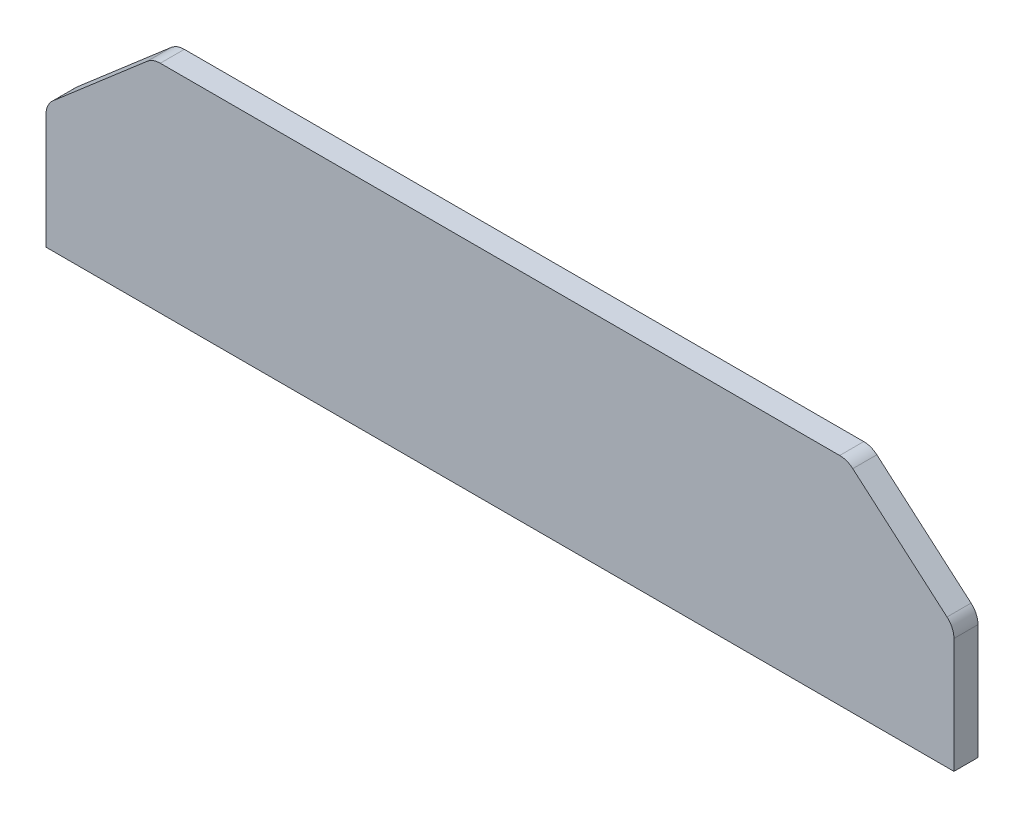
SolidWorks part; units mm, degrees
ref_plane "Front Plane" through (0, 0, 0) normal (0, 0, 1) x (1, 0, 0)
ref_plane "Top Plane" through (0, 0, 0) normal (0, 1, 0) x (1, 0, 0)
ref_plane "Right Plane" through (0, 0, 0) normal (1, 0, 0) x (0, 0, -1)
sketch "Sketch2" plane through (0, 3, 0) normal (0, 0, 1) x (1, 0, 0)
  line L2 (-56.625, -30) -> (56.625, -30)
  line L3 (56.625, -30) -> (56.625, -15.6446)
  line L4 (55.7585, -13.7521) -> (44.0052, -3.6075)
  line L5 (42.3717, -3) -> (-42.3717, -3)
  line L6 (-44.0052, -3.6075) -> (-55.7585, -13.7521)
  line L7 (-56.625, -15.6446) -> (-56.625, -30)
  arc A0 (56.625, -15.6446) -> (55.7585, -13.7521) centre (54.125, -15.6446) ccw
  arc A1 (44.0052, -3.6075) -> (42.3717, -3) centre (42.3717, -5.5) ccw
  arc A2 (-55.7585, -13.7521) -> (-56.625, -15.6446) centre (-54.125, -15.6446) ccw
  arc A3 (-42.3717, -3) -> (-44.0052, -3.6075) centre (-42.3717, -5.5) ccw
  point P0 (0, -3)
  point P8 (0, -30)
  point P15 (56.625, -14.5)
  point P18 (43.3014, -3)
  point P23 (-43.3014, -3)
  dimension "D6" = 2.5
  dimension "D1" = 113.25
  dimension "D2" = 15.5
  dimension "D3" = 27
  dimension "D4" = 86.6028
extrude "Boss-Extrude1" add sketch "Sketch2" along normal blind 3
